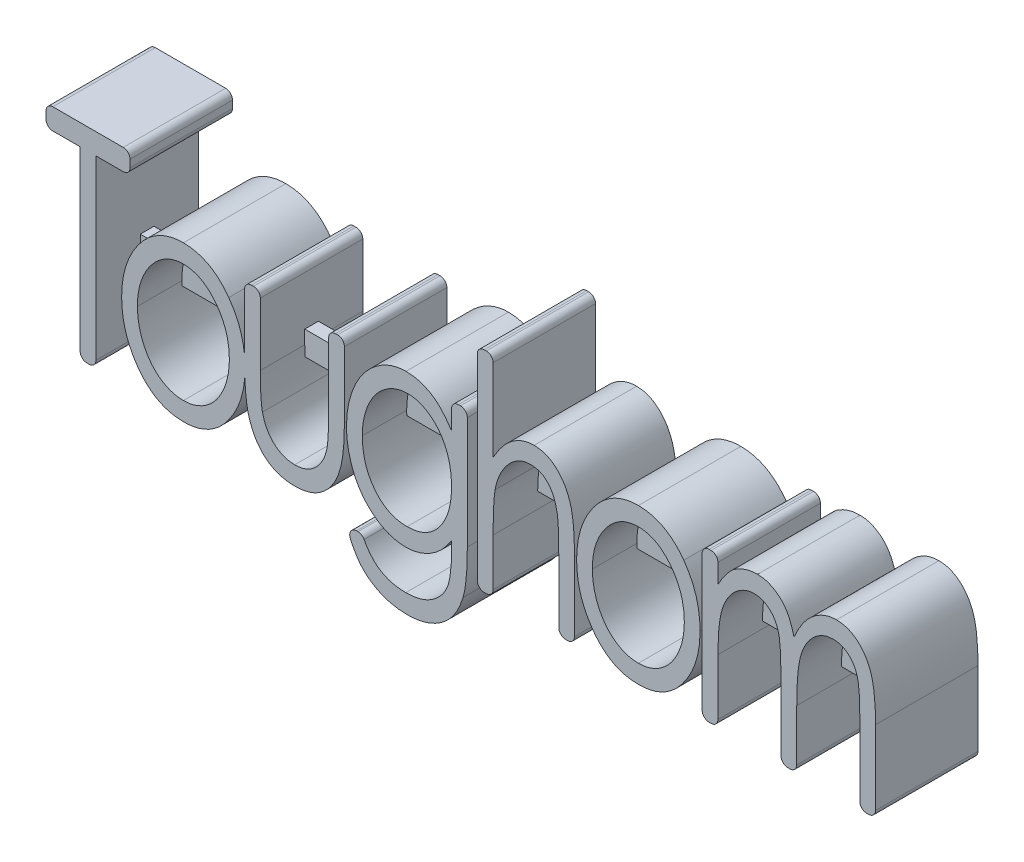
SolidWorks part; units mm, degrees
ref_plane "Front Plane" through (0, 0, 0) normal (0, 0, 1) x (1, 0, 0)
ref_plane "Top Plane" through (0, 0, 0) normal (0, 1, 0) x (1, 0, 0)
ref_plane "Right Plane" through (0, 0, 0) normal (1, 0, 0) x (0, 0, -1)
sketch "Sketch1" plane through (0, 0, 0) normal (0, 0, 1) x (1, 0, 0)
  line L1 (-57.5, 1.75) -> (57.5, 1.75)
  line L2 (-57.5, 1.75) -> (-57.5, -1.75)
  line L3 (-57.5, -1.75) -> (57.5, -1.75)
  line L4 (57.5, 1.75) -> (57.5, -1.75)
  line L5 (-57.5, 1.75) -> (57.5, -1.75) construction
  line L6 (-57.5, -1.75) -> (57.5, 1.75) construction
  point P0 (0, 0)
  dimension "D1" = 3.5
  dimension "D2" = 115
extrude "Boss-Extrude1" add sketch "Sketch1" along normal mid plane 2
sketch "Sketch2" plane through (0, 0, 0) normal (0, 0, 1) x (1, 0, 0)
  line L0 (0, 0) -> (0, -12) construction
  line L1 (-79.262, -12) -> (76.9306, -12) construction
  text T0 "Toughom" font "Century Gothic" height 30
  point P4 (0, 0)
  point P10 (0, -12)
  dimension "D1" = 12
extrude "Boss-Extrude2" add sketch "Sketch2" along normal mid plane 15
fillet "Fillet10" radius 1 28 edges at (58.6035, -12, 0) (56.2958, -12, 0) (47.065, -12, 0) (44.7574, -12, 0) (35.5266, -12, 0) (33.2189, -12, 0) (35.5266, 9.9231, 0) (33.2189, 9.9231, 0) (14.5266, -12, 0) (12.2189, -12, 0) (2.6035, -12, 0) (0.2958, -12, 0) (-16.5503, -13.5385, 0) (-18.858, -13.5385, 0) (2.6035, 18.7692, 0) (0.2958, 18.7692, 0) (-1.1657, 9.9231, 0) (-3.4734, 9.9231, 0) (-55.5503, -12, 0) (-57.858, -12, 0) (-62.858, 14.9231, 0) (-50.5503, 14.9231, 0) (-50.5503, 18, 0) (-62.858, 18, 0) (-19.1657, 9.9231, 0) (-21.4734, 9.9231, 0) (-31.4734, 9.9231, 0) (-33.7811, 9.9231, 0)
sketch "Sketch3" plane through (0, 0, 0) normal (0, 0, 1) x (1, 0, 0)
  line L0 (-57.858, -11) -> (-57.858, 14.9231) construction
  line L1 (-57.858, 8.043) -> (-57.858, 5.043)
  line L2 (-57.858, 1.043) -> (-57.858, -1.957)
  arc A0 (-57.858, 8.043) -> (-57.858, -1.957) centre (-57.858, 3.043) ccw
  arc A1 (-57.858, 5.043) -> (-57.858, 1.043) centre (-57.858, 3.043) ccw
  point P6 (0, 0)
  point P8 (0, 0)
  point P9 (-57.858, 0.9723)
  dimension "D1" = 5
  dimension "D2" = 2
extrude "Boss-Extrude3" add sketch "Sketch3" along normal mid plane 4
fillet "Fillet12" radius 1 8 edges at (-62.858, 3.043, 2) (-62.858, 3.043, -2) (-57.858, -0.457, -2) (-57.858, 6.543, -2) (-57.858, 6.543, 2) (-57.858, -0.457, 2) (-57.858, -1.957, 0) (-57.858, 8.043, 0)
